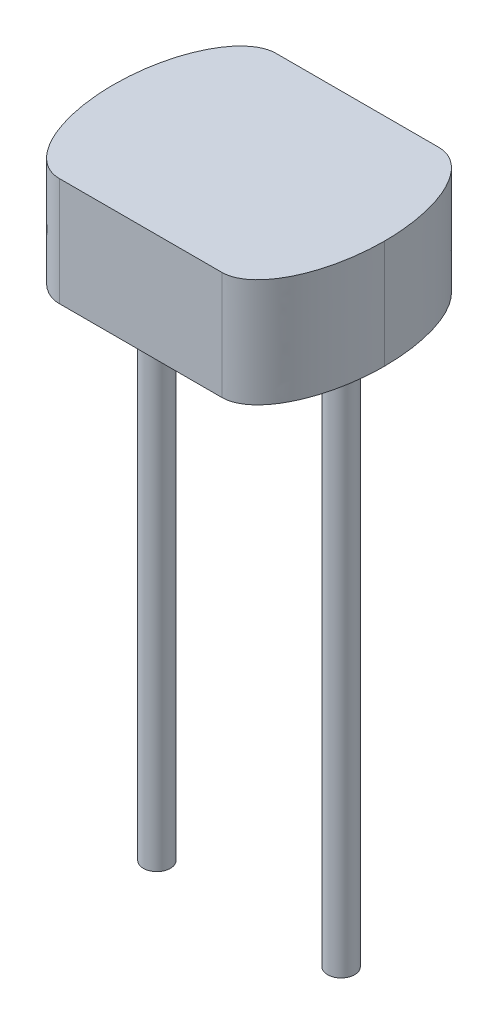
SolidWorks part; units mm, degrees
ref_plane "Front Plane" through (0, 0, 0) normal (0, 0, 1) x (1, 0, 0)
ref_plane "Top Plane" through (0, 0, 0) normal (0, 1, 0) x (1, 0, 0)
ref_plane "Right Plane" through (0, 0, 0) normal (1, 0, 0) x (0, 0, -1)
sketch "Sketch1" plane through (0, 0, 0) normal (0, 1, 0) x (1, 0, 0)
  line L1 (-2.5, -2) -> (2.5, -2)
  line L2 (-2.5, -2) -> (-2.5, 2)
  line L3 (-2.5, 2) -> (2.5, 2)
  line L4 (2.5, -2) -> (2.5, 2)
  point P4 (0, 2)
  point P6 (2.5, 0)
  dimension "D1" = 5
  dimension "D2" = 4
extrude "Boss-Extrude1" add sketch "Sketch1" along normal blind 2
sketch "Sketch2" plane through (0, 0, 0) normal (0, -1, 0) x (1, 0, 0)
  line L0 (-2.5, -2) -> (-2.5, 2) construction
  line L1 (0, 0) -> (0, 2) construction
  line L2 (-2.5, 2) -> (2.5, 2) construction
  circle A0 centre (-1.7, 0) radius 0.25
  circle A1 centre (1.7, 0) radius 0.25
  dimension "D2" = 0.5
  dimension "D1" = 0.8
extrude "Boss-Extrude2" add sketch "Sketch2" along normal blind 10
fillet "Fillet1" radius 1 2 edges at (-2.5, 1, -2) (2.5, 1, 2) second distance 2 first distance on face at (0, 1, -2) first distance on face at (0, 1, 2)
fillet "Fillet2" radius 2 2 edges at (-2.5, 1, 2) (2.5, 1, -2) second distance 1 first distance on face at (-2.5, 1.25, 0.5) first distance on face at (2.5, 1.25, -0.5)
equation "\"leg_length\"=10"
equation "\"D1@Boss-Extrude2\"=\"leg_length\""
